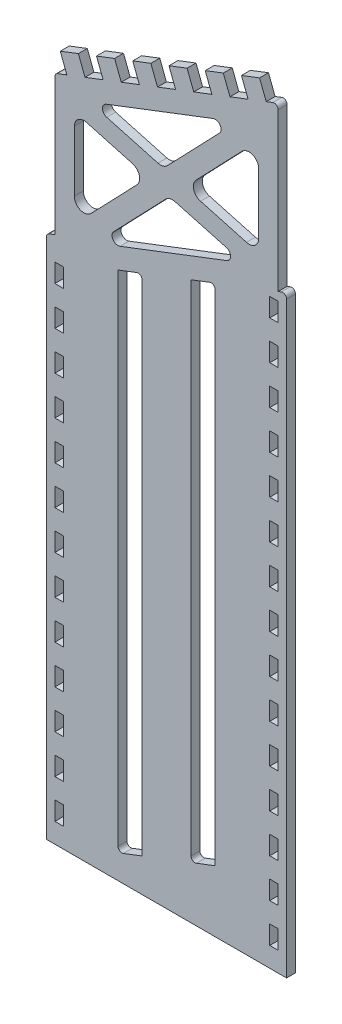
SolidWorks part; units mm, degrees
ref_plane "Front Plane" through (0, 0, 0) normal (0, 0, 1) x (1, 0, 0)
ref_plane "Top Plane" through (0, 0, 0) normal (0, 1, 0) x (1, 0, 0)
ref_plane "Right Plane" through (0, 0, 0) normal (1, 0, 0) x (0, 0, -1)
sketch "Sketch1" plane through (0, 0, 0) normal (0, 0, 1) x (1, 0, 0)
  line L0 (-36.5179, 109.22) -> (36.5179, 109.22) construction
  line L1 (-36.5179, 109.22) -> (36.5179, 137.2558)
  line L2 (-36.5179, 109.22) -> (-36.5179, -109.22)
  line L3 (-36.5179, -109.22) -> (36.5179, -109.22)
  line L4 (36.5179, 137.2558) -> (36.5179, -109.22)
  point P4 (0, 123.2379)
  point P7 (-36.5179, 0)
  dimension "D1" = 78.232
  dimension "D2" = 218.44
  dimension "D3" = 21
extrude "Boss-Extrude1" add sketch "Sketch1" along normal mid plane 2.921
sketch "Sketch2" plane through (0, 0, 1.4605) normal (0, 0, 1) x (1, 0, 0)
  line L0 (-36.5179, -109.22) -> (-33.5969, -109.22)
  line L1 (-36.5179, 109.22) -> (36.5179, 109.22)
  line L2 (-36.5179, 109.22) -> (-36.5179, -109.22)
  line L4 (36.5179, 109.22) -> (36.5179, -109.22)
  line L5 (-36.5179, 109.22) -> (-33.5969, 109.22)
  line L6 (-36.5179, 109.22) -> (-36.5179, -109.22)
  line L7 (-36.5179, -109.22) -> (-33.5969, -109.22)
  line L8 (-33.5969, 109.22) -> (-33.5969, -109.22)
  line L9 (36.5179, -109.22) -> (33.5969, -109.22)
  line L10 (36.5179, -109.22) -> (36.5179, 109.22)
  line L11 (36.5179, 109.22) -> (33.5969, 109.22)
  line L12 (33.5969, -109.22) -> (33.5969, 109.22)
  line L13 (33.5969, -109.22) -> (36.5179, -109.22)
  line L14 (-33.5969, -109.22) -> (33.5969, -109.22)
  line L29 (0, 123.2379) -> (0, -109.22) construction
  line L31 (36.5179, 137.2558) -> (-36.5179, 109.22) construction
  point P10 (-41.8689, -88.479)
  point P13 (0, 0)
  point P14 (-4.4, -109.22)
  point P15 (-48.4481, -73.343)
  point P16 (0, -109.22)
  point P17 (0.6468, -109.22)
  dimension "D1" = 2.921
  dimension "D2" = 2.921
sketch "Sketch3" plane through (-41.2311, 107.4108, 0) normal (-0.3584, 0.9336, 0) x (0.9336, 0.3584, 0)
  line L0 (83.2805, 1.4605) -> (5.0485, 1.4605) construction
  line L1 (79.0895, 1.4605) -> (72.7395, 1.4605)
  line L2 (79.0895, 1.4605) -> (79.0895, -1.4605)
  line L3 (79.0895, -1.4605) -> (72.7395, -1.4605)
  line L4 (72.7395, 1.4605) -> (72.7395, -1.4605)
  line L5 (83.2805, -1.4605) -> (5.0485, -1.4605) construction
  line L6 (83.2805, -1.4605) -> (83.2805, 1.4605) construction
  line L7 (66.3895, 1.4605) -> (66.3895, -1.4605)
  line L8 (66.3895, 1.4605) -> (60.0395, 1.4605)
  line L9 (60.0395, 1.4605) -> (60.0395, -1.4605)
  line L10 (66.3895, -1.4605) -> (60.0395, -1.4605)
  line L11 (53.6895, 1.4605) -> (53.6895, -1.4605)
  line L12 (53.6895, 1.4605) -> (47.3395, 1.4605)
  line L13 (47.3395, 1.4605) -> (47.3395, -1.4605)
  line L14 (53.6895, -1.4605) -> (47.3395, -1.4605)
  line L15 (40.9895, 1.4605) -> (40.9895, -1.4605)
  line L16 (40.9895, 1.4605) -> (34.6395, 1.4605)
  line L17 (34.6395, 1.4605) -> (34.6395, -1.4605)
  line L18 (40.9895, -1.4605) -> (34.6395, -1.4605)
  line L19 (28.2895, 1.4605) -> (28.2895, -1.4605)
  line L20 (28.2895, 1.4605) -> (21.9395, 1.4605)
  line L21 (21.9395, 1.4605) -> (21.9395, -1.4605)
  line L22 (28.2895, -1.4605) -> (21.9395, -1.4605)
  line L23 (15.5895, 1.4605) -> (15.5895, -1.4605)
  line L24 (15.5895, 1.4605) -> (9.2395, 1.4605)
  line L25 (9.2395, 1.4605) -> (9.2395, -1.4605)
  line L26 (15.5895, -1.4605) -> (9.2395, -1.4605)
  line L27 (79.0895, 1.4605) -> (66.3895, 1.4605) construction
  point P10 (72.7395, 0)
  dimension "D1" = 4.191
  dimension "D2" = 6.35
  dimension "D4" = 12.7
  dimension "D3" = 6
extrude "Boss-Extrude2" add sketch "Sketch3" along normal blind 6.0452
sketch "Sketch5" plane through (0, 0, 1.4605) normal (0, 0, 1) x (1, 0, 0)
  line L0 (0, 123.2379) -> (0, -109.22) construction
  line L1 (-15.875, 63.8041) -> (-8.001, 66.8266)
  line L2 (-15.875, 63.8041) -> (-15.875, -101.2959)
  line L3 (-15.875, -101.2959) -> (-8.001, -98.2734)
  line L4 (-8.001, 66.8266) -> (-8.001, -98.2734)
  line L5 (8.001, 72.9692) -> (15.875, 75.9918)
  line L6 (8.001, 72.9692) -> (8.001, -92.1308)
  line L7 (8.001, -92.1308) -> (15.875, -89.1082)
  line L8 (15.875, 75.9918) -> (15.875, -89.1082)
  line L9 (-36.5179, -109.22) -> (36.5179, -109.22) construction
  line L11 (-33.5969, -109.22) -> (33.5969, -109.22) construction
  line L12 (-8.001, 66.8266) -> (8.001, 72.9692) construction
  line L13 (-20.7488, 115.2732) -> (-26.6771, 112.9976) construction
  line L14 (-36.5179, -109.22) -> (36.5179, -81.1842) construction
  line L15 (36.5179, -109.22) -> (36.5179, 137.2558) construction
  line L17 (36.5179, -109.22) -> (36.5179, 137.2558) construction
  line L20 (-36.5179, 109.22) -> (-36.5179, -109.22) construction
  line L22 (-32.6053, 110.7219) -> (-36.5179, 109.22) construction
  line L23 (2.9641, 124.3757) -> (-2.9641, 122.1001) construction
  point P13 (2.8085, -109.22)
  point P16 (0, 69.8979)
  dimension "D1" = 31.75
  dimension "D2" = 21
  dimension "D3" = 165.1
  dimension "D4" = 7.874
extrude "Cut-Extrude2" cut sketch "Sketch5" against normal through all
sketch "Sketch6" plane through (0, 0, 1.4605) normal (0, 0, 1) x (1, 0, 0)
  line L0 (-39.2679, 54.8244) -> (39.2679, 84.9715)
  line L1 (39.2679, 84.9715) -> (39.2679, -109.22)
  line L2 (39.2679, -109.22) -> (-39.2679, -109.22)
  line L3 (-39.2679, -109.22) -> (-39.2679, 54.8244)
  line L4 (-8.001, 66.8266) -> (-15.875, 63.8041) construction
  line L5 (-36.5179, 109.22) -> (-36.5179, -109.22) construction
  line L6 (36.5179, -109.22) -> (36.5179, 137.2558) construction
  line L7 (-36.5179, -109.22) -> (36.5179, -109.22) construction
  line L8 (-36.5179, 55.88) -> (-36.5179, -109.22)
  line L9 (36.5179, -109.22) -> (36.5179, 83.9158)
  line L10 (0, -109.22) -> (0, 69.8979) construction
  line L11 (-36.5179, -96.647) -> (-33.7679, -96.647)
  line L12 (-36.5179, -96.647) -> (-36.5179, -102.743)
  line L13 (-36.5179, -102.743) -> (-33.7679, -102.743)
  line L14 (-33.7679, -96.647) -> (-33.7679, -102.743)
  line L15 (36.5179, -102.743) -> (33.7679, -102.743)
  line L16 (33.7679, -96.647) -> (33.7679, -102.743)
  line L17 (36.5179, -96.647) -> (33.7679, -96.647)
  line L18 (36.5179, -96.647) -> (36.5179, -102.743)
  line L19 (-39.2679, 54.8244) -> (-39.2679, 62.4444)
  line L20 (-39.2679, 62.4444) -> (-36.5179, 63.5)
  line L21 (-36.5179, 63.5) -> (-36.5179, 55.88)
  point P22 (-35.1429, -102.743)
  line M13 (-36.5179, 109.22) -> (-36.5179, -109.22)
  line M15 (36.5179, -109.22) -> (36.5179, 137.2558)
  dimension "D1" = 2.75
  dimension "D2" = 2.75
  dimension "D3" = 2.75
  dimension "D4" = 6.096
  dimension "D5" = 6.477
  dimension "D6" = 7.62
extrude "Boss-Extrude3" add sketch "Sketch6" against normal blind 2.921 contours L3 L2 L0 M13 | L2 L1 L0 M15 | L20 L19 L0 M13 region at (-37.8929, 59.1622, 1.4605) region at (-37.8915, -26.9336, 1.4605) region at (37.8942, -12.3879, 1.4605)
extrude "Cut-Extrude3" cut sketch "Sketch6<3>" against normal through all contours L14 L11 L8 L13 region at (-35.1429, -99.695, 1.4605)
sketch "Sketch6<3>" plane through (0, 0, 1.4605) normal (0, 0, 1) x (1, 0, 0) same geometry as "Sketch6"
extrude "Cut-Extrude4" cut sketch "Sketch6<4>" against normal through all contours L9 L17 L16 L15 region at (35.1429, -99.695, 1.4605)
sketch "Sketch6<4>" plane through (0, 0, 1.4605) normal (0, 0, 1) x (1, 0, 0) same geometry as "Sketch6"
pattern_linear "LPattern1" count 13 spacing 12.7 along (0, 1, 0) of "Cut-Extrude3"
pattern_linear "LPattern2" count 15 spacing 12.7 along (0, 1, 0) of "Cut-Extrude4"
sketch "Sketch8" plane through (0, 0, 1.4605) normal (0, 0, 1) x (1, 0, 0)
  line L0 (-36.5179, 109.22) -> (36.5179, 137.2558) construction
  line L1 (36.5179, 137.2558) -> (36.5179, 83.9158) construction
  line L2 (36.5179, 83.9158) -> (-36.5179, 55.88) construction
  line L3 (-36.5179, 55.88) -> (-36.5179, 109.22) construction
  line L4 (-30.1679, 104.8558) -> (30.1679, 88.2801) construction
  line L5 (30.1679, 128.0165) -> (-30.1679, 65.1193) construction
  line L6 (-30.1679, 65.1193) -> (-30.1679, 104.8558)
  line L7 (-30.1679, 104.8558) -> (30.1679, 128.0165)
  line L8 (30.1679, 128.0165) -> (30.1679, 88.2801)
  line L9 (30.1679, 88.2801) -> (-30.1679, 65.1193)
  line L10 (27.8767, 130.2145) -> (-32.4592, 67.3172)
  line L11 (-31.009, 101.7942) -> (29.3268, 85.2185)
  line L12 (32.4592, 125.8186) -> (-27.8767, 62.9214)
  line L13 (-29.3268, 107.9173) -> (31.009, 91.3416)
  dimension "D1" = 6.35
  dimension "D2" = 3.175
  dimension "D3" = 3.175
extrude "Cut-Extrude5" cut sketch "Sketch8" against normal through all contours L11 L6 L10 | L11 L12 L9 | L7 L13 L10 | L12 L13 L8 region at (-22.1059, 88.7292, 1.4605) region at (0.9822, 82.3863, 1.4605) region at (-0.9822, 110.7495, 1.4605) region at (22.1059, 104.4067, 1.4605)
fillet "Fillet1" radius 1.27 8 edges at (8.001, -92.1308, 0) (-15.875, -101.2959, 0) (-8.001, 66.8266, 0) (15.875, 75.9918, 0) (-39.2679, 62.4444, 0) (39.2679, 84.9715, 0) (-36.5179, 109.22, 0) (36.5179, 137.2558, 0)
fillet "Fillet2" radius 3.175 8 edges at (30.1679, 91.5727, 0) (30.1679, 123.4301, 0) (-30.1679, 69.7057, 0) (-30.1679, 101.5631, 0) (-5.9818, 94.9186, 0) (5.9818, 98.2172, 0) (0.9822, 93.0054, 0) (-0.9822, 100.1304, 0)
fillet "Fillet3" radius 1.905 4 edges at (-23.2039, 67.7925, 0) (25.1684, 86.3609, 0) (23.2039, 125.3433, 0) (-25.1684, 106.7749, 0)
